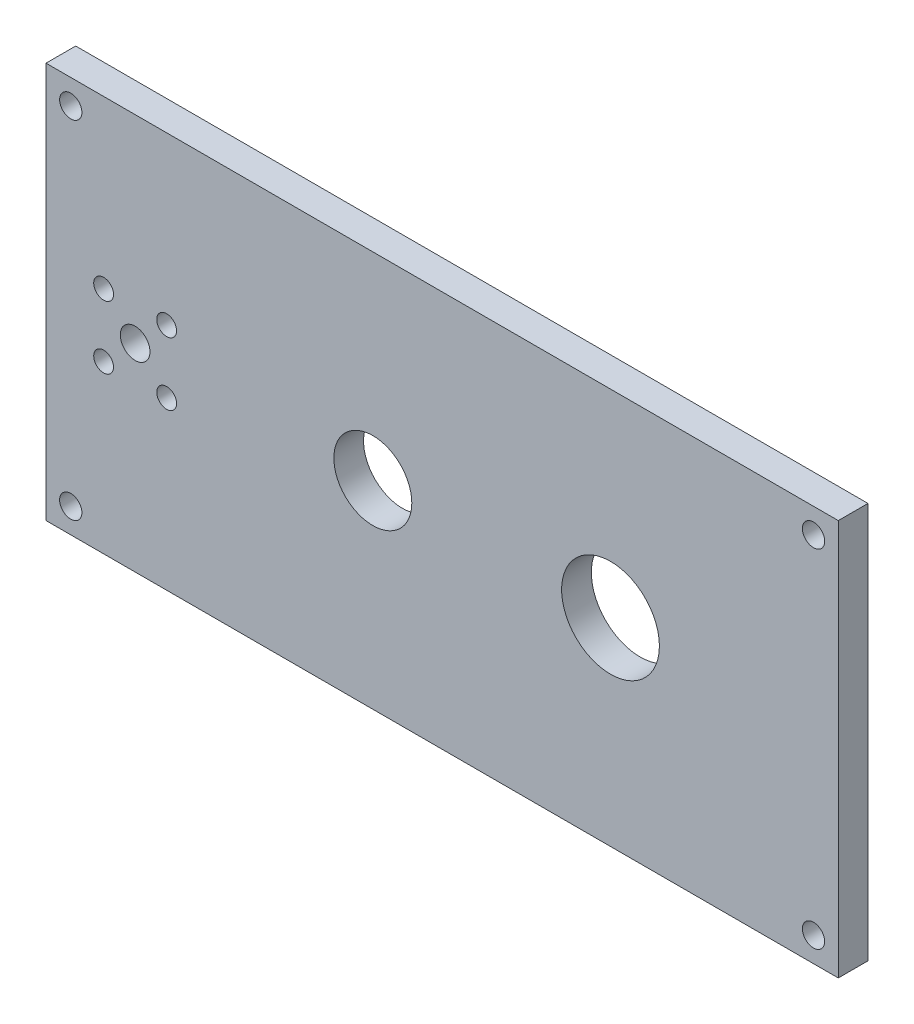
SolidWorks part; units mm, degrees
ref_plane "Front Plane" through (0, 0, 0) normal (0, 0, 1) x (1, 0, 0)
ref_plane "Top Plane" through (0, 0, 0) normal (0, 1, 0) x (1, 0, 0)
ref_plane "Right Plane" through (0, 0, 0) normal (1, 0, 0) x (0, 0, -1)
sketch "Sketch1" plane through (0, 0, 0) normal (0, 0, 1) x (1, 0, 0)
  line L1 (0, 0) -> (80, 0)
  line L2 (0, 0) -> (0, 40)
  line L3 (0, 40) -> (80, 40)
  line L4 (80, 0) -> (80, 40)
  dimension "D1" = 80
  dimension "D2" = 40
extrude "Boss-Extrude1" add sketch "Sketch1" along normal blind 3 contours L3 L4 L1 L2
sketch "Sketch2" plane through (0, 0, 3) normal (0, 0, 1) x (1, 0, 0)
  line L0 (0, 20) -> (80, 20) construction
  line L1 (0, 0) -> (0, 40) construction
  line L2 (80, 0) -> (80, 40) construction
  line L3 (9, 20) -> (13.5, 20) construction
  line L4 (4.318, 15.318) -> (13.682, 15.318) construction
  line L5 (4.318, 15.318) -> (4.318, 24.682) construction
  line L6 (4.318, 24.682) -> (13.682, 24.682) construction
  line L7 (13.682, 15.318) -> (13.682, 24.682) construction
  line L8 (4.318, 15.318) -> (13.682, 24.682) construction
  line L9 (4.318, 24.682) -> (13.682, 15.318) construction
  line L10 (40, 40) -> (40, 0) construction
  line L11 (0, 40) -> (80, 40) construction
  line L12 (0, 0) -> (80, 0) construction
  circle A1 centre (33, 20) radius 3.9365
  circle A2 centre (57, 20) radius 4.9365
  circle A3 centre (12.182, 23.182) radius 1
  circle A4 centre (9, 20) radius 4.5 construction
  circle A5 centre (12.182, 16.818) radius 1
  circle A6 centre (5.818, 16.818) radius 1
  circle A7 centre (5.818, 23.182) radius 1
  circle A8 centre (2.5, 37.5) radius 1.125
  circle A9 centre (77.5, 37.5) radius 1.125
  circle A10 centre (77.5, 2.5) radius 1.125
  circle A11 centre (2.5, 2.5) radius 1.125
  circle A12 centre (9, 20) radius 1.5
  point P6 (9, 20)
  dimension "D1" = 9
  dimension "D2" = 7.873
  dimension "D3" = 9.873
  dimension "D5" = 2
  dimension "D7" = 9
  dimension "D9" = 2.25
  dimension "D12" = 3
  dimension "D4" = 24
  dimension "D6" = 24
  dimension "D8" = 1.5
  dimension "D10" = 2.5
  dimension "D11" = 2.5
extrude "Cut-Extrude1" cut sketch "Sketch2" against normal through all contours A1 L0 | L0 A1 | A2 L0 | L0 A2 | A7 | A3 | A5 | A6 | A12 | A11 | A8 | A9 | A10 region at (33, 20, 3) region at (57, 20, 3) region at (12.182, 23.182, 3) region at (12.182, 16.818, 3) region at (5.818, 16.818, 3) region at (5.818, 23.182, 3) region at (9, 20, 3)
